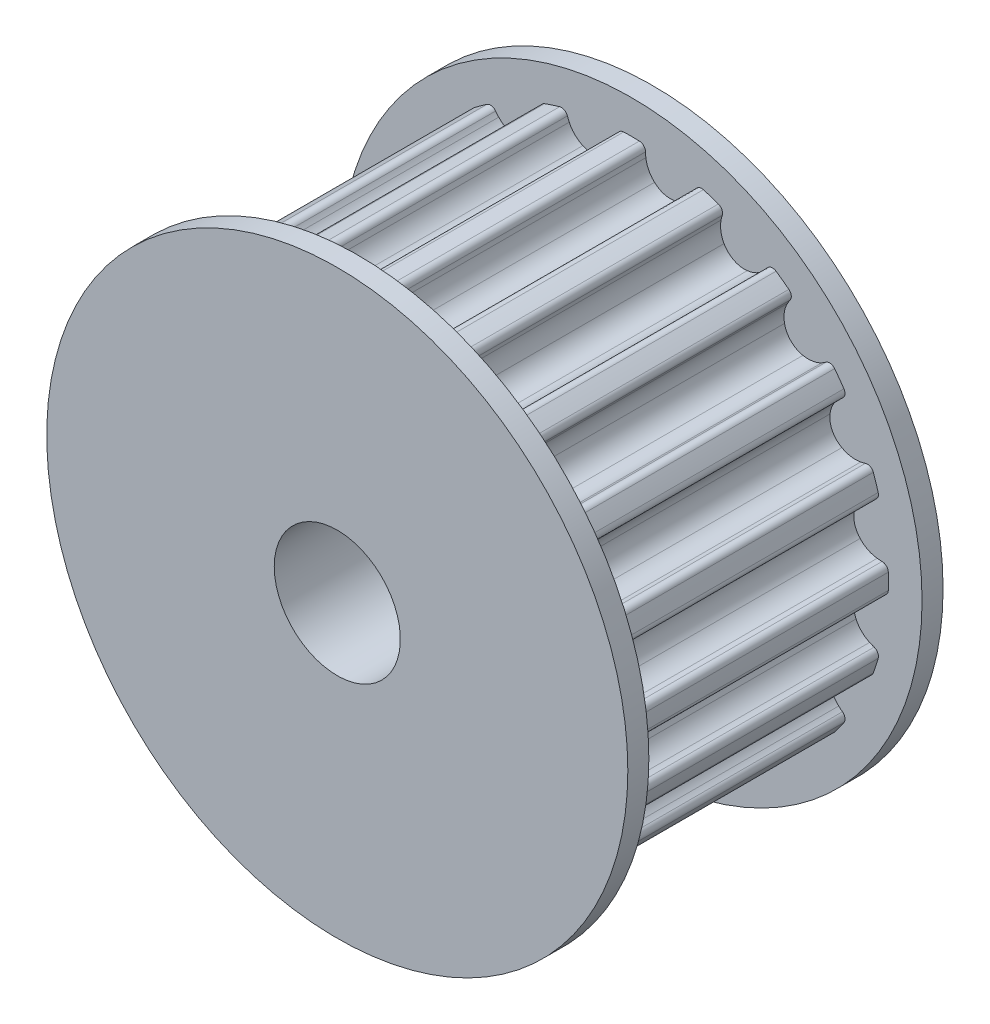
SolidWorks part; units mm, degrees
material "PET"
ref_plane "Front Plane" through (0, 0, 0) normal (0, 0, 1) x (1, 0, 0)
ref_plane "Top Plane" through (0, 0, 0) normal (0, 1, 0) x (1, 0, 0)
ref_plane "Right Plane" through (0, 0, 0) normal (1, 0, 0) x (0, 0, -1)
sketch "Sketch1" plane through (0, 0, 0) normal (0, 0, 1) x (1, 0, 0)
  line L0 (0, 0) -> (0, 6.3662) construction
  line L1 (0, 0) -> (0.9959, 6.2878) construction
  line L2 (0, 0) -> (1.3887, 6.2129) construction
  circle A0 centre (0, 0) radius 6.3662 construction
  circle A1 centre (0, 0) radius 5.3622 construction
  circle A2 centre (0, 0) radius 6.1122 construction
  arc A3 (0.8388, 5.2962) -> (0.5472, 5.4384) centre (0.9257, 5.8443) cw
  arc A4 (0.3406, 5.8443) -> (0.3333, 5.9601) centre (1.3333, 5.965) cw
  circle A5 centre (0, 0) radius 5.9622 construction
  arc A6 (-0.188, 6.1093) -> (0.188, 6.1093) centre (0, 0) cw
  arc A7 (0.188, 6.1093) -> (0.3333, 5.9601) centre (0.1833, 5.9594) cw
  arc A8 (0.3406, 5.8443) -> (0.5472, 5.4384) centre (1.0004, 5.9245) ccw
  arc A9 (-0.8388, 5.2962) -> (-0.5472, 5.4384) centre (-0.9257, 5.8443) ccw
  arc A10 (-0.3406, 5.8443) -> (-0.5472, 5.4384) centre (-1.0004, 5.9245) cw
  arc A11 (-0.3406, 5.8443) -> (-0.3333, 5.9601) centre (-1.3333, 5.965) ccw
  arc A12 (-0.188, 6.1093) -> (-0.3333, 5.9601) centre (-0.1833, 5.9594) ccw
  arc A13 (-0.8388, 5.2962) -> (0.8388, 5.2962) centre (0, 0) cw
  dimension "D1" = 12.7324
  dimension "D6" = 0.555
  dimension "D7" = 1
  dimension "D9" = 0.15
  dimension "D2" = 9
  dimension "D3" = 3.6
  dimension "D4" = 1.004
  dimension "D5" = 0.75
  dimension "D8" = 0.15
extrude "Boss-Extrude1" add sketch "Sketch1" along normal blind 6.5
ref_axis "Axis1" through (0, 0, -0.375) along (0, 0, 1)
pattern_circular "CirPattern1" count 20 over 360 about axis through (0, 0, -0.375) along (0, 0, 1) of bodies 107
sketch "Sketch2" plane through (0, 0, 0) normal (0, 0, -1) x (-1, 0, 0)
  circle A0 centre (0, 0) radius 5.3622
  arc A1 (0.8388, 5.2962) -> (-0.8388, 5.2962) centre (0, 0) ccw construction
extrude "Boss-Extrude2" add sketch "Sketch2" against normal up to surface (6.5 mm away)
sketch "Schizzo1" plane through (0, 0, 6.5) normal (0, 0, 1) x (1, 0, 0)
  circle A0 centre (0, 0) radius 6.9122
  arc A1 (-6.1093, 0.188) -> (-6.1093, -0.188) centre (0, 0) ccw construction
  dimension "D1" = 0.8
extrude "Estrusione-Estrusione1" add sketch "Schizzo1" along normal blind 0.5
ref_plane "Piano1" through (0, 0, 3.25) normal (0, 0, -1) x (-1, 0, 0)
mirror "Specchia1" about plane through (0, 0, 3.25) normal (0, 0, -1) of "Estrusione-Estrusione1"
sketch "Schizzo3" plane through (0, 0, -0.5) normal (0, 0, -1) x (-1, 0, 0)
  circle A0 centre (0, 0) radius 1.5
  dimension "D1" = 3
extrude "Taglio-Estrusione2" cut sketch "Schizzo3" against normal through all
sketch "Schizzo2" plane through (0, 0, -0.5) normal (0, 0, -1) x (-1, 0, 0)
  arc A0 (-0.1172, 3.5721) -> (-0.645, 4.6555) centre (-1.906, 3.3711) ccw
  arc A1 (0.1172, 3.5721) -> (-0.1172, 3.5721) centre (0, 0) ccw
  arc A2 (0.645, 4.6555) -> (0.1172, 3.5721) centre (1.906, 3.3711) ccw
  arc A3 (1.1857, 4.548) -> (0.645, 4.6555) centre (0, 0) ccw
  arc A4 (1.2587, 3.345) -> (1.1857, 4.548) centre (-0.4708, 3.8439) ccw
  arc A5 (1.4753, 3.2553) -> (1.2587, 3.345) centre (0, 0) ccw
  arc A6 (2.3775, 4.0543) -> (1.4753, 3.2553) centre (3.051, 2.3851) ccw
  arc A7 (2.8359, 3.748) -> (2.3775, 4.0543) centre (0, 0) ccw
  arc A8 (2.4429, 2.6087) -> (2.8359, 3.748) centre (1.036, 3.7314) ccw
  arc A9 (2.6087, 2.4429) -> (2.4429, 2.6087) centre (0, 0) ccw
  arc A10 (3.748, 2.8359) -> (2.6087, 2.4429) centre (3.7314, 1.036) ccw
  arc A11 (4.0543, 2.3775) -> (3.748, 2.8359) centre (0, 0) ccw
  arc A12 (3.2553, 1.4753) -> (4.0543, 2.3775) centre (2.3851, 3.051) ccw
  arc A13 (3.345, 1.2587) -> (3.2553, 1.4753) centre (0, 0) ccw
  arc A14 (4.548, 1.1857) -> (3.345, 1.2587) centre (3.8439, -0.4708) ccw
  arc A15 (4.6555, 0.645) -> (4.548, 1.1857) centre (0, 0) ccw
  arc A16 (3.5721, 0.1172) -> (4.6555, 0.645) centre (3.3711, 1.906) ccw
  arc A17 (3.5721, -0.1172) -> (3.5721, 0.1172) centre (0, 0) ccw
  arc A18 (4.6555, -0.645) -> (3.5721, -0.1172) centre (3.3711, -1.906) ccw
  arc A19 (4.548, -1.1857) -> (4.6555, -0.645) centre (0, 0) ccw
  arc A20 (3.345, -1.2587) -> (4.548, -1.1857) centre (3.8439, 0.4708) ccw
  arc A21 (3.2553, -1.4753) -> (3.345, -1.2587) centre (0, 0) ccw
  arc A22 (4.0543, -2.3775) -> (3.2553, -1.4753) centre (2.3851, -3.051) ccw
  arc A23 (3.748, -2.8359) -> (4.0543, -2.3775) centre (0, 0) ccw
  arc A24 (2.6087, -2.4429) -> (3.748, -2.8359) centre (3.7314, -1.036) ccw
  arc A25 (2.4429, -2.6087) -> (2.6087, -2.4429) centre (0, 0) ccw
  arc A26 (2.8359, -3.748) -> (2.4429, -2.6087) centre (1.036, -3.7314) ccw
  arc A27 (2.3775, -4.0543) -> (2.8359, -3.748) centre (0, 0) ccw
  arc A28 (1.4753, -3.2553) -> (2.3775, -4.0543) centre (3.051, -2.3851) ccw
  arc A29 (1.2587, -3.345) -> (1.4753, -3.2553) centre (0, 0) ccw
  arc A30 (1.1857, -4.548) -> (1.2587, -3.345) centre (-0.4708, -3.8439) ccw
  arc A31 (0.645, -4.6555) -> (1.1857, -4.548) centre (0, 0) ccw
  arc A32 (0.1172, -3.5721) -> (0.645, -4.6555) centre (1.906, -3.3711) ccw
  arc A33 (-0.1172, -3.5721) -> (0.1172, -3.5721) centre (0, 0) ccw
  arc A34 (-0.645, -4.6555) -> (-0.1172, -3.5721) centre (-1.906, -3.3711) ccw
  arc A35 (-1.1857, -4.548) -> (-0.645, -4.6555) centre (0, 0) ccw
  arc A36 (-1.2587, -3.345) -> (-1.1857, -4.548) centre (0.4708, -3.8439) ccw
  arc A37 (-1.4753, -3.2553) -> (-1.2587, -3.345) centre (0, 0) ccw
  arc A38 (-2.3775, -4.0543) -> (-1.4753, -3.2553) centre (-3.051, -2.3851) ccw
  arc A39 (-2.8359, -3.748) -> (-2.3775, -4.0543) centre (0, 0) ccw
  arc A40 (-2.4429, -2.6087) -> (-2.8359, -3.748) centre (-1.036, -3.7314) ccw
  arc A41 (-2.6087, -2.4429) -> (-2.4429, -2.6087) centre (0, 0) ccw
  arc A42 (-3.748, -2.8359) -> (-2.6087, -2.4429) centre (-3.7314, -1.036) ccw
  arc A43 (-4.0543, -2.3775) -> (-3.748, -2.8359) centre (0, 0) ccw
  arc A44 (-3.2553, -1.4753) -> (-4.0543, -2.3775) centre (-2.3851, -3.051) ccw
  arc A45 (-3.345, -1.2587) -> (-3.2553, -1.4753) centre (0, 0) ccw
  arc A46 (-4.548, -1.1857) -> (-3.345, -1.2587) centre (-3.8439, 0.4708) ccw
  arc A47 (-4.6555, -0.645) -> (-4.548, -1.1857) centre (0, 0) ccw
  arc A48 (-3.5721, -0.1172) -> (-4.6555, -0.645) centre (-3.3711, -1.906) ccw
  arc A49 (-3.5721, 0.1172) -> (-3.5721, -0.1172) centre (0, 0) ccw
  arc A50 (-4.6555, 0.645) -> (-3.5721, 0.1172) centre (-3.3711, 1.906) ccw
  arc A51 (-4.548, 1.1857) -> (-4.6555, 0.645) centre (0, 0) ccw
  arc A52 (-3.345, 1.2587) -> (-4.548, 1.1857) centre (-3.8439, -0.4708) ccw
  arc A53 (-3.2553, 1.4753) -> (-3.345, 1.2587) centre (0, 0) ccw
  arc A54 (-4.0543, 2.3775) -> (-3.2553, 1.4753) centre (-2.3851, 3.051) ccw
  arc A55 (-3.748, 2.8359) -> (-4.0543, 2.3775) centre (0, 0) ccw
  arc A56 (-2.6087, 2.4429) -> (-3.748, 2.8359) centre (-3.7314, 1.036) ccw
  arc A57 (-2.4429, 2.6087) -> (-2.6087, 2.4429) centre (0, 0) ccw
  arc A58 (-2.8359, 3.748) -> (-2.4429, 2.6087) centre (-1.036, 3.7314) ccw
  arc A59 (-2.3775, 4.0543) -> (-2.8359, 3.748) centre (0, 0) ccw
  arc A60 (-1.4753, 3.2553) -> (-2.3775, 4.0543) centre (-3.051, 2.3851) ccw
  arc A61 (-1.2587, 3.345) -> (-1.4753, 3.2553) centre (0, 0) ccw
  arc A62 (-1.1857, 4.548) -> (-1.2587, 3.345) centre (0.4708, 3.8439) ccw
  arc A63 (-0.645, 4.6555) -> (-1.1857, 4.548) centre (0, 0) ccw
  point P128 (0, 0)
extrude "Taglio-Estrusione1" cut sketch "Schizzo2" against normal blind 5.1
equation "\"NumTeeth\"= 20'The number of teeth that the pulley has"
equation "\"ToothPitch\"= 2.00mm'Distance between 2 teeth"
equation "\"PulleyDia\"= \"NumTeeth\" * \"ToothPitch\" / PI"
equation "\"ToothAng\"= ( 360deg / \"NumTeeth\" ) * 1deg"
equation "\"TransOffsetAngle\"= \"ToothAng\" * .2deg"
equation "\"ShoulderRad\"= 0.15mm"
equation "\"RootRad\"= 0.555mm"
equation "\"TransRad\"= 1mm"
equation "\"ToothHeight\"= 0.75mm"
equation "\"PLD\"= 0.254mm"
equation "\"D1@CirPattern1\"=\"NumTeeth\""
equation "\"D1@Sketch1\"=\"PulleyDia\""
equation "\"D7@Sketch1\"=\"TransRad\""
equation "\"D9@Sketch1\"=\"ShoulderRad\""
equation "\"D6@Sketch1\"=\"RootRad\""
equation "\"D3@Sketch1\"=\"TransOffsetAngle\""
equation "\"D5@Sketch1\"=\"ToothHeight\""
equation "\"D2@Sketch1\"=\"ToothAng\"/2"
equation "\"D4@Sketch1\"=\"PLD\"+\"ToothHeight\""
equation "\"D8@Sketch1\"=\"ShoulderRad\""
equation "\"altezza\"= 6.5mm"
equation "\"D1@Boss-Extrude1\"=\"altezza\""
